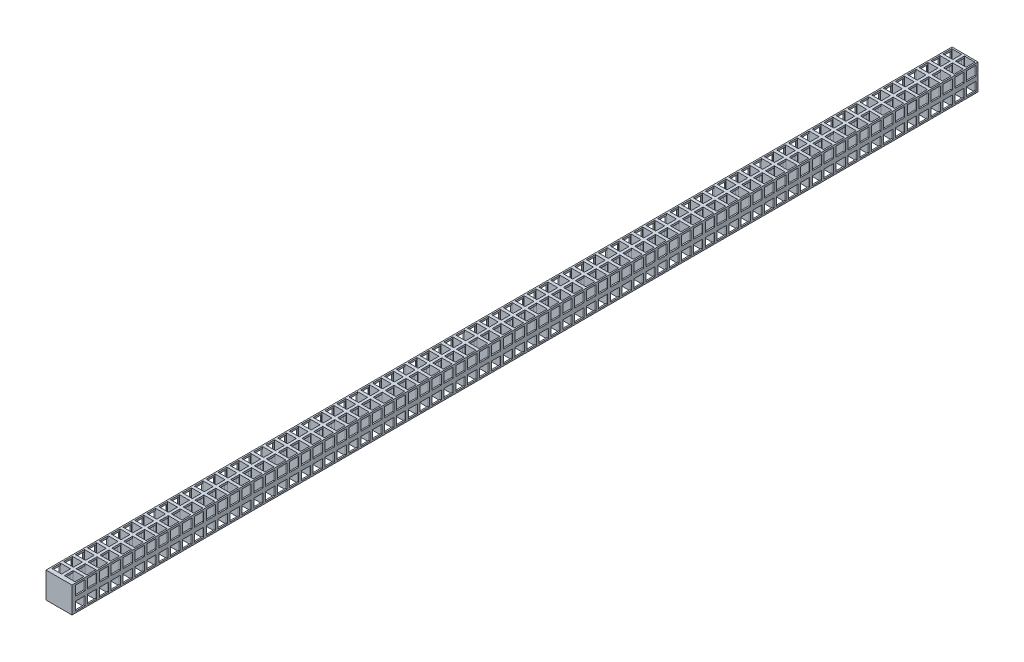
SolidWorks part; units mm, degrees
ref_plane "Alzado" through (0, 0, 0) normal (0, 0, 1) x (1, 0, 0)
ref_plane "Planta" through (0, 0, 0) normal (0, 1, 0) x (1, 0, 0)
ref_plane "Vista lateral" through (0, 0, 0) normal (1, 0, 0) x (0, 0, -1)
sketch "Croquis1" plane through (0, 0, 0) normal (0, 0, 1) x (1, 0, 0)
  line L1 (-175, 175) -> (175, 175)
  line L2 (-175, 175) -> (-175, -175)
  line L3 (-175, -175) -> (175, -175)
  line L4 (175, 175) -> (175, -175)
  line L5 (-175, 175) -> (175, -175) construction
  line L6 (-175, -175) -> (175, 175) construction
  point P0 (0, 0)
  dimension "D1" = 350
  dimension "D2" = 350
extrude "Saliente-Extruir1" add sketch "Croquis1" along normal blind 12200
sketch "Croquis2" plane through (0, 175, 0) normal (0, 1, 0) x (1, 0, 0)
  line L1 (-155.9826, -21.6819) -> (-22.9987, -21.6819)
  line L2 (-155.9826, -21.6819) -> (-155.9826, -141.6282)
  line L3 (-155.9826, -141.6282) -> (-22.9987, -141.6282)
  line L4 (-22.9987, -21.6819) -> (-22.9987, -141.6282)
  line L5 (-155.9826, -21.6819) -> (-22.9987, -141.6282) construction
  line L6 (-155.9826, -141.6282) -> (-22.9987, -21.6819) construction
  line L7 (13.5067, -21.6819) -> (156.9206, -21.6819)
  line L8 (13.5067, -21.6819) -> (13.5067, -141.6282)
  line L9 (13.5067, -141.6282) -> (156.9206, -141.6282)
  line L10 (156.9206, -21.6819) -> (156.9206, -141.6282)
  line L11 (13.5067, -21.6819) -> (156.9206, -141.6282) construction
  line L12 (13.5067, -141.6282) -> (156.9206, -21.6819) construction
  point P0 (-89.4906, -81.6551)
  point P6 (85.2136, -81.6551)
extrude "Cortar-Extruir1" cut sketch "Croquis2" against normal blind 12200
pattern_linear "MatrizL1" count 76 spacing 160 along (0, 0, 1) of "Cortar-Extruir1"
sketch "Croquis3" plane through (175, 0, 0) normal (1, 0, 0) x (0, 0, -1)
  line L1 (-26.6974, 150.2665) -> (-151.6043, 150.2665)
  line L2 (-26.6974, 150.2665) -> (-26.6974, 21.5745)
  line L3 (-26.6974, 21.5745) -> (-151.6043, 21.5745)
  line L4 (-151.6043, 150.2665) -> (-151.6043, 21.5745)
  line L5 (-26.6974, 150.2665) -> (-151.6043, 21.5745) construction
  line L6 (-26.6974, 21.5745) -> (-151.6043, 150.2665) construction
  line L7 (-26.6974, -37.1663) -> (-151.6043, -37.1663)
  line L8 (-26.6974, -37.1663) -> (-26.6974, -154.5031)
  line L9 (-26.6974, -154.5031) -> (-151.6043, -154.5031)
  line L10 (-151.6043, -37.1663) -> (-151.6043, -154.5031)
  line L11 (-26.6974, -37.1663) -> (-151.6043, -154.5031) construction
  line L12 (-26.6974, -154.5031) -> (-151.6043, -37.1663) construction
  point P0 (-89.1509, 85.9205)
  point P5 (-89.1509, -95.8347)
  point P10 (-89.1509, 85.9205)
  point P11 (-89.1509, -95.8347)
extrude "Cortar-Extruir2" cut sketch "Croquis3" against normal blind 12200
pattern_linear "MatrizL2" count 76 spacing 160 along (0, 0, 1) of "Cortar-Extruir2"
